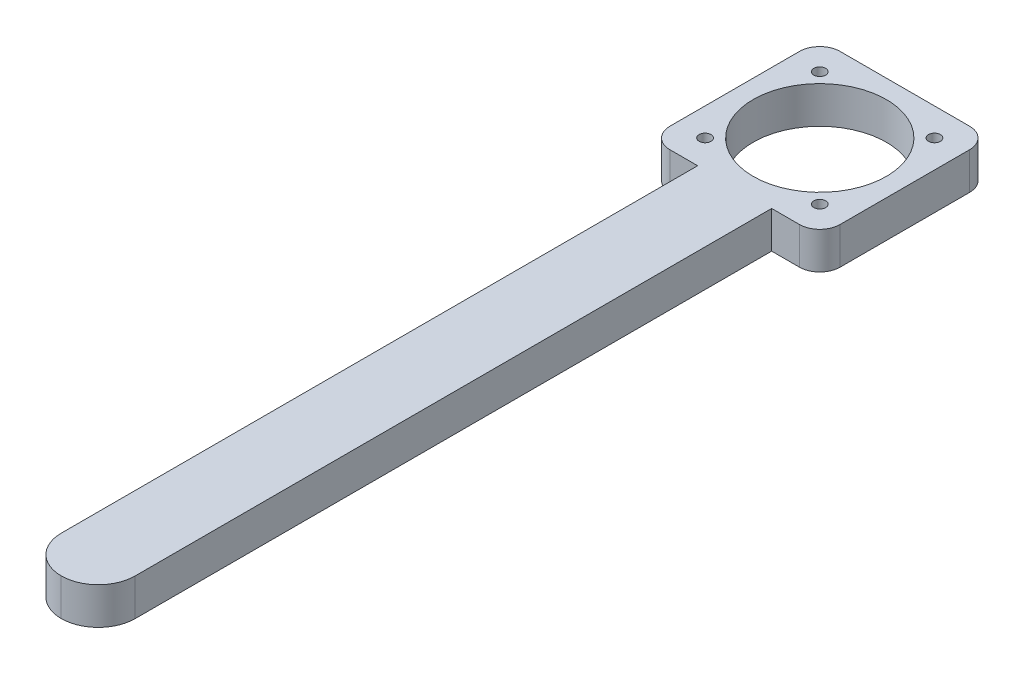
SolidWorks part; units mm, degrees
ref_plane "前视基准面" through (0, 0, 0) normal (0, 0, 1) x (1, 0, 0)
ref_plane "上视基准面" through (0, 0, 0) normal (0, 1, 0) x (1, 0, 0)
ref_plane "右视基准面" through (0, 0, 0) normal (1, 0, 0) x (0, 0, -1)
other "Configuration Table"
sketch "草图2" plane through (0, 0, 0) normal (0, 1, 0) x (1, 0, 0)
  line L1 (-23, -23) -> (23, -23)
  line L2 (-23, -23) -> (-23, 23)
  line L3 (-23, 23) -> (23, 23)
  line L4 (23, -23) -> (23, 23)
  line L5 (-23, -23) -> (23, 23) construction
  line L6 (-23, 23) -> (23, -23) construction
  circle A0 centre (0, 0) radius 18
extrude "凸台-拉伸1" add sketch "草图2" along normal blind 10
fillet "圆角1" radius 5.5 4 edges at (23, 5, 23) (23, 5, -23) (-23, 5, -23) (-23, 5, 23)
sketch "草图3" plane through (0, 10, 0) normal (0, 1, 0) x (1, 0, 0)
  line L1 (-15.5, -15.5) -> (15.5, -15.5)
  line L2 (-15.5, -15.5) -> (-15.5, 15.5)
  line L3 (-15.5, 15.5) -> (15.5, 15.5)
  line L4 (15.5, -15.5) -> (15.5, 15.5)
  line L5 (-15.5, -15.5) -> (15.5, 15.5) construction
  line L6 (-15.5, 15.5) -> (15.5, -15.5) construction
  circle A0 centre (-15.5, 15.5) radius 1.6
  circle A1 centre (15.5, 15.5) radius 1.6
  circle A2 centre (-15.5, -15.5) radius 1.6
  circle A3 centre (15.5, -15.5) radius 1.6
  point P0 (0, 0)
extrude "切除-拉伸1" cut sketch "草图3" against normal through all contours A2 | A0 | A1 | A3
sketch "草图4" plane through (0, 10, 0) normal (0, 1, 0) x (1, 0, 0)
  line L0 (-10, -23) -> (-10, -205)
  line L1 (-10, -23) -> (10, -23)
  line L2 (-10, -205) -> (10, -205)
  line L3 (10, -23) -> (10, -205)
extrude "凸台-拉伸2" add sketch "草图4" against normal blind 10
fillet "圆角2" radius 10 2 edges at (-10, 5, 205) (10, 5, 205)
sketch "草图5" plane through (0, 10, 0) normal (0, 1, 0) x (1, 0, 0)
  line L0 (-3, -198.41) -> (-3, -193.59)
  line L1 (-3, -198.41) -> (3, -198.41)
  line L2 (-3, -193.59) -> (3, -193.59)
  line L3 (3, -198.41) -> (3, -193.59)
  line L4 (-3, -198.41) -> (3, -193.59) construction
  line L5 (-3, -193.59) -> (3, -198.41) construction
